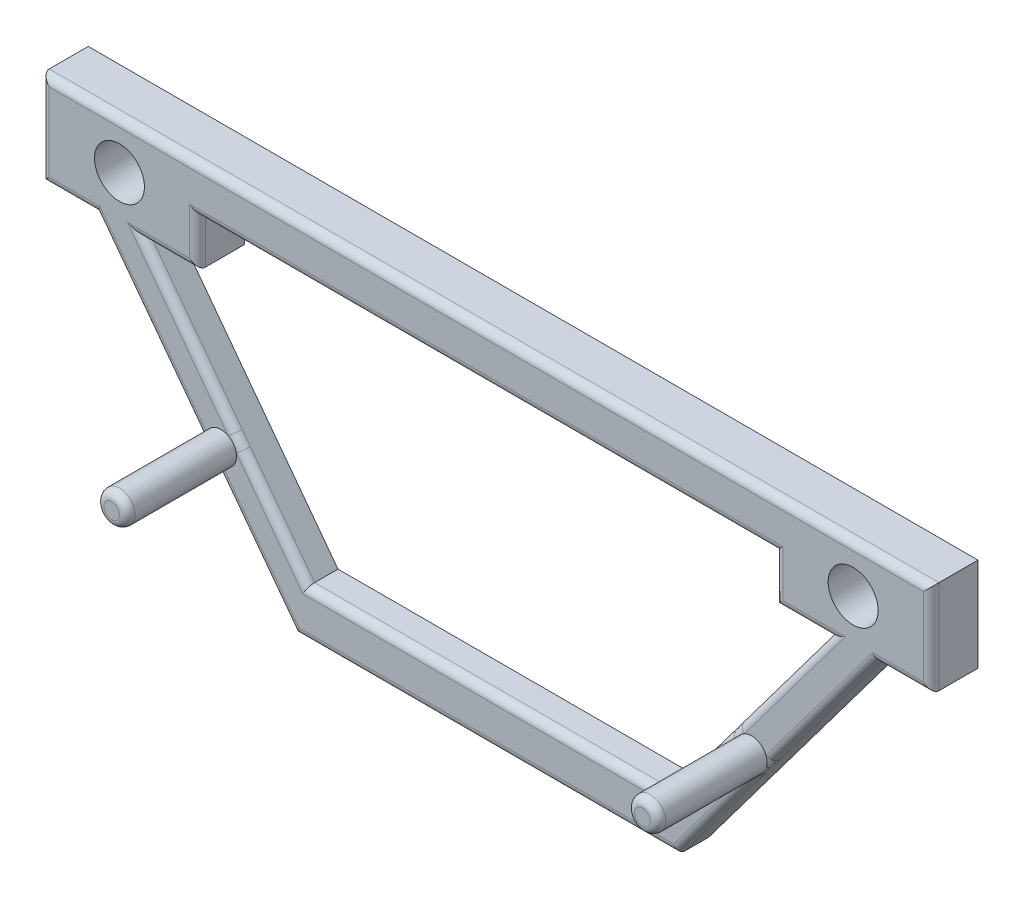
SolidWorks part; units mm, degrees
ref_plane "Ebene vorne" through (0, 0, 0) normal (0, 0, 1) x (1, 0, 0)
ref_plane "Ebene oben" through (0, 0, 0) normal (0, 1, 0) x (1, 0, 0)
ref_plane "Ebene rechts" through (0, 0, 0) normal (1, 0, 0) x (0, 0, -1)
sketch "Skizze1" plane through (0, 0, 0) normal (0, 0, 1) x (1, 0, 0)
  line L0 (0, 0) -> (0, 46.9928) construction
  line L3 (28.5, 17) -> (28.5, 23)
  line L5 (18.5, 20) -> (18.5, 17)
  line L13 (18.5, 17) -> (22, 17)
  line L14 (28.5, 17) -> (25, 17)
  line L15 (22, 17) -> (11.5, 3)
  line L16 (25, 17) -> (12.25, 0)
  line L17 (11.5, 3) -> (-11.5, 3)
  line L18 (12.25, 0) -> (-12.25, 0)
  line L19 (-25, 17) -> (-12.25, 0)
  line L20 (-22, 17) -> (-11.5, 3)
  line L21 (-28.5, 17) -> (-25, 17)
  line L22 (-18.5, 17) -> (-22, 17)
  line L23 (-18.5, 20) -> (-18.5, 17)
  line L24 (-28.5, 23) -> (28.5, 23)
  line L25 (-28.5, 17) -> (-28.5, 23)
  line L26 (22.5, 18.75) -> (22.5, 4.6099) construction
  line L28 (-18.5, 20) -> (18.5, 20)
  point P9 (0, 3)
  point P12 (0, 3)
  point P26 (28.5, 20)
  dimension "D1" = 23
  dimension "D2" = 57
  dimension "D3" = 6
  dimension "D4" = 3
  dimension "D5" = 3
  dimension "D6" = 3.5
  dimension "D7" = 10
  dimension "D8" = 3
  dimension "D9" = 23
extrude "Aufsatz-Linear austragen1" add sketch "Skizze1" along normal blind 3
sketch "Skizze3" plane through (0, 0, 3) normal (0, 0, 1) x (1, 0, 0)
  line L0 (0, 0) -> (0, 62.4514) construction
  line L1 (23.5, 17) -> (23.5, 34.1584) construction
  line L2 (25, 17) -> (28.5, 17) construction
  line L3 (28.5, 17) -> (28.5, 23) construction
  line L5 (-23.5, 17) -> (-23.5, 34.1584) construction
  circle A0 centre (23.5, 20) radius 1.6
  circle A1 centre (-23.5, 20) radius 1.6
  dimension "D2" = 3.2
  dimension "D1" = 5
  dimension "D3" = 3
extrude "Bohrungen" cut sketch "Skizze3" against normal through all
sketch "Skizze4" plane through (28.5, 0, 0) normal (1, 0, 0) x (0, 0, -1)
  line L0 (-1, 0) -> (-1, 17)
  line L3 (-1, 17) -> (0, 17)
  line L4 (0, 17) -> (0, 0)
  line L5 (0, 0) -> (-1, 0)
  dimension "D1" = 1
extrude "Dicken_anpassung" cut sketch "Skizze4" against normal through all
sketch "Skizze5" plane through (0, 0, 3) normal (0, 0, 1) x (1, 0, 0)
  line L0 (0, 0) -> (0, 27.2221) construction
  line L1 (28.5, 23) -> (-28.5, 23) construction
  circle A0 centre (17, 8) radius 1
  circle A1 centre (-17, 8) radius 1
  dimension "D2" = 2
  dimension "D1" = 17
  dimension "D3" = 15
extrude "Aufsatz-Linear austragen2" add sketch "Skizze5" along normal blind 7
fillet "Verrundung2" radius 0.5 20 edges at (15.025, 3.7, 3) (-15.025, 3.7, 3) (-18, 8, 10) (18, 8, 10) (0, 0, 3) (21.4, 12.2, 3) (26.75, 17, 3) (28.5, 20, 3) (0, 23, 3) (-28.5, 20, 3) (-26.75, 17, 3) (-21.4, 12.2, 3) (-20.25, 17, 3) (-18.5, 18.5, 3) (0, 20, 3) (18.5, 18.5, 3) (20.25, 17, 3) (16.75, 10, 3) (0, 3, 3) (-16.75, 10, 3)
